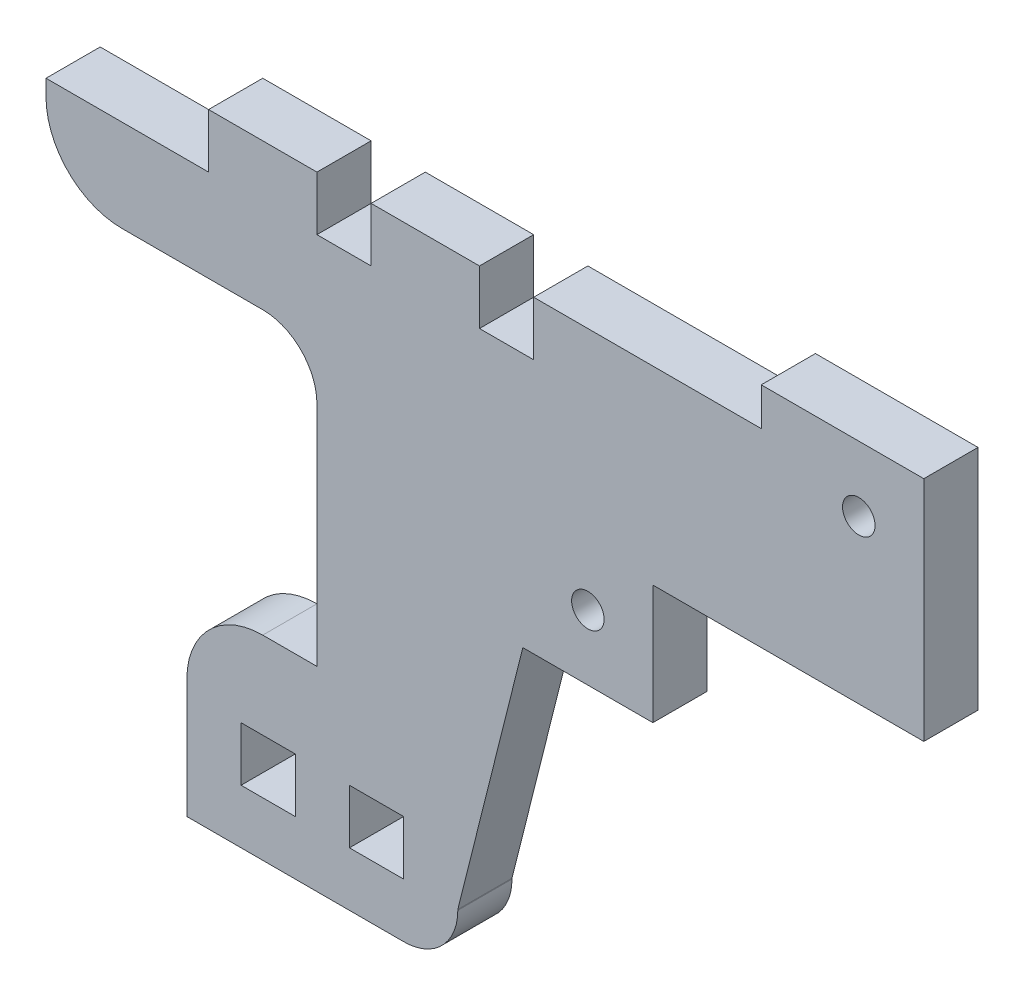
SolidWorks part; units mm, degrees
ref_plane "Plan de face" through (0, 0, 0) normal (0, 0, 1) x (1, 0, 0)
ref_plane "Plan de dessus" through (0, 0, 0) normal (0, 1, 0) x (1, 0, 0)
ref_plane "Plan de droite" through (0, 0, 0) normal (1, 0, 0) x (0, 0, -1)
sketch "Esquisse1" plane through (0, 0, 0) normal (0, 0, 1) x (1, 0, 0)
  line L0 (31, 19) -> (43, 19)
  line L1 (5, 0) -> (10, 0)
  line L2 (0, 0) -> (0, 8)
  line L3 (12, 42.5) -> (17, 42.5)
  line L4 (68, 30) -> (68, 51)
  line L5 (27, 42.5) -> (32, 42.5)
  line L6 (2, 42.5) -> (2, 47.5)
  line L7 (2, 47.5) -> (12, 47.5)
  line L8 (12, 42.5) -> (12, 47.5)
  line L9 (15, 0) -> (20, 0)
  line L10 (17, 42.5) -> (17, 47.5)
  line L11 (17, 47.5) -> (27, 47.5)
  line L12 (27, 42.5) -> (27, 47.5)
  line L13 (15, 0) -> (15, -5)
  line L14 (10, -5) -> (5, -5)
  line L15 (10, 0) -> (10, -5)
  line L16 (5, 0) -> (5, -5)
  line L17 (-13, 42.5) -> (2, 42.5)
  line L18 (0, 0) -> (0, -5.81)
  line L19 (-13, 34) -> (-13, 42.5)
  line L20 (0, 8) -> (12, 8)
  line L22 (-13, 34) -> (12, 34)
  line L23 (12, 8) -> (12, 34)
  line L24 (20, 0) -> (20, -5)
  line L25 (43, 19) -> (43, 30)
  line L26 (43, 30) -> (68, 30)
  line L27 (53, 47.5) -> (53, 51)
  line L28 (53, 51) -> (68, 51)
  line L29 (32, 42.5) -> (32, 47.5)
  line L30 (31, 19) -> (25, -4.929)
  line L31 (20, -5) -> (15, -5)
  line L32 (25, -4.929) -> (25, -10)
  line L33 (25, -10) -> (0, -10)
  line L34 (0, -5.81) -> (0, -10)
  line L35 (32, 47.5) -> (53, 47.5)
  circle A0 centre (62, 45) radius 1.5
  circle A1 centre (37, 25) radius 1.5
  circle A2 centre (37, 25) radius 1.5 construction
  circle A3 centre (62, 45) radius 1.5 construction
  dimension "D9" = 3
  dimension "D11" = 6
  dimension "D14" = 6
  dimension "D12" = 6
  dimension "D15" = 66
  dimension "D3" = 10
  dimension "D4" = 5
  dimension "D5" = 5
  dimension "D6" = 25
  dimension "D7" = 8
  dimension "D8" = 26
  dimension "D10" = 5
  dimension "D13" = 12
  dimension "D16" = 6
  dimension "D17" = 15
  dimension "D18" = 42.5
  dimension "D20" = 5
  dimension "D21" = 5
  dimension "D22" = 5
  dimension "D23" = 5
  dimension "D24" = 25
  dimension "D25" = 15
extrude "Boss.-Extru.1" add sketch "Esquisse1" along normal blind 5
fillet "Congé1" radius 7 2 edges at (0, 8, 2.5) (-13, 34, 2.5)
fillet "Congé2" radius 5 1 edges at (12, 34, 2.5)
fillet "Congé3" radius 5 1 edges at (25, -10, 2.5)
